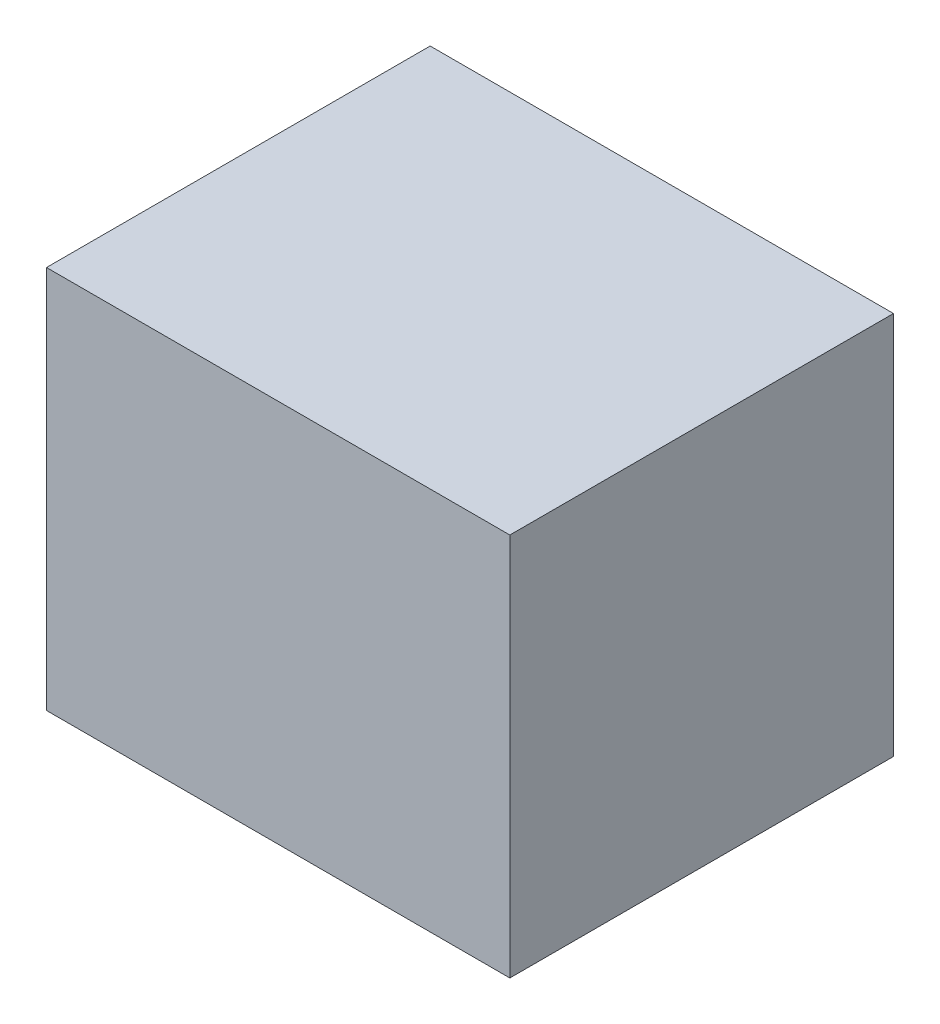
SolidWorks part; units mm, degrees
ref_plane "Ebene vorne" through (0, 0, 0) normal (0, 0, 1) x (1, 0, 0)
ref_plane "Ebene oben" through (0, 0, 0) normal (0, 1, 0) x (1, 0, 0)
ref_plane "Ebene rechts" through (0, 0, 0) normal (1, 0, 0) x (0, 0, -1)
sketch "Skizze1" plane through (0, 0, 0) normal (0, 0, 1) x (1, 0, 0)
  line L1 (-39.25, -32.5) -> (39.25, -32.5)
  line L2 (-39.25, -32.5) -> (-39.25, 32.5)
  line L3 (-39.25, 32.5) -> (39.25, 32.5)
  line L4 (39.25, -32.5) -> (39.25, 32.5)
  line L5 (-39.25, -32.5) -> (39.25, 32.5) construction
  line L6 (-39.25, 32.5) -> (39.25, -32.5) construction
  point P0 (0, 0)
  dimension "D1" = 65
  dimension "D2" = 78.5
extrude "Aufsatz-Linear austragen1" add sketch "Skizze1" along normal blind 65
